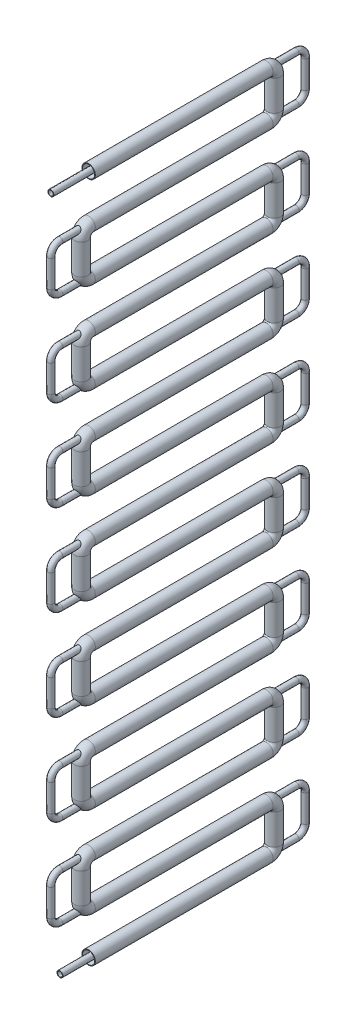
SolidWorks part; units mm, degrees
ref_plane "Alzado" through (0, 0, 0) normal (0, 0, 1) x (1, 0, 0)
ref_plane "Planta" through (0, 0, 0) normal (0, 1, 0) x (1, 0, 0)
ref_plane "Vista lateral" through (0, 0, 0) normal (1, 0, 0) x (0, 0, -1)
sketch "Seccion agua" plane through (0, 0, 0) normal (0, 0, 1) x (1, 0, 0)
  circle A2 centre (0, 0) radius 8
  circle A3 centre (0, 0) radius 8.8
  dimension "D1" = 16
  dimension "D2" = 0.8
sketch "Recorrido agua" plane through (0, 0, 0) normal (1, 0, 0) x (0, 0, -1)
  line L0 (0, 0) -> (235, 0)
  line L1 (245, -10) -> (245, -50)
  line L2 (235, -60) -> (0, -60)
  line L3 (-10, -70) -> (-10, -110)
  line L4 (0, -120) -> (235, -120)
  line L5 (0, 0) -> (0, -100.3636) construction
  line L6 (235, 0) -> (235, -103.1636) construction
  line L7 (245, -130) -> (245, -170)
  line L8 (235, -180) -> (0, -180)
  line L9 (-10, -190) -> (-10, -230)
  line L10 (0, -240) -> (235, -240)
  line L11 (245, -250) -> (245, -290)
  line L12 (235, -300) -> (0, -300)
  line L13 (-10, -310) -> (-10, -350)
  line L14 (0, -360) -> (235, -360)
  line L15 (245, -370) -> (245, -410)
  line L16 (235, -420) -> (0, -420)
  line L17 (-10, -430) -> (-10, -470)
  line L18 (0, -480) -> (235, -480)
  line L19 (245, -490) -> (245, -530)
  line L20 (235, -540) -> (0, -540)
  line L21 (-10, -550) -> (-10, -590)
  line L22 (0, -600) -> (235, -600)
  line L23 (245, -610) -> (245, -650)
  line L24 (235, -660) -> (0, -660)
  line L25 (-10, -670) -> (-10, -710)
  line L26 (0, -720) -> (235, -720)
  line L27 (245, -730) -> (245, -770)
  line L28 (235, -780) -> (0, -780)
  line L29 (-10, -790) -> (-10, -830)
  line L30 (0, -840) -> (235, -840)
  line L31 (245, -850) -> (245, -890)
  line L32 (235, -900) -> (0, -900)
  line L35 (0, -960) -> (235, -960) [skipped]
  line L36 (-10, -910) -> (-10, -950) [skipped]
  arc A0 (235, 0) -> (245, -10) centre (235, -10) cw
  arc A1 (245, -50) -> (235, -60) centre (235, -50) cw
  arc A2 (0, -60) -> (-10, -70) centre (0, -70) ccw
  arc A3 (-10, -110) -> (0, -120) centre (0, -110) ccw
  arc A4 (245, -170) -> (235, -180) centre (235, -170) cw
  arc A5 (0, -180) -> (-10, -190) centre (0, -190) ccw
  arc A6 (235, -120) -> (245, -130) centre (235, -130) cw
  arc A7 (-10, -230) -> (0, -240) centre (0, -230) ccw
  arc A8 (245, -290) -> (235, -300) centre (235, -290) cw
  arc A9 (0, -300) -> (-10, -310) centre (0, -310) ccw
  arc A10 (235, -240) -> (245, -250) centre (235, -250) cw
  arc A11 (-10, -350) -> (0, -360) centre (0, -350) ccw
  arc A12 (245, -410) -> (235, -420) centre (235, -410) cw
  arc A13 (0, -420) -> (-10, -430) centre (0, -430) ccw
  arc A14 (235, -360) -> (245, -370) centre (235, -370) cw
  arc A15 (-10, -470) -> (0, -480) centre (0, -470) ccw
  arc A16 (245, -530) -> (235, -540) centre (235, -530) cw
  arc A17 (0, -540) -> (-10, -550) centre (0, -550) ccw
  arc A18 (235, -480) -> (245, -490) centre (235, -490) cw
  arc A19 (-10, -590) -> (0, -600) centre (0, -590) ccw
  arc A20 (245, -650) -> (235, -660) centre (235, -650) cw
  arc A21 (0, -660) -> (-10, -670) centre (0, -670) ccw
  arc A22 (235, -600) -> (245, -610) centre (235, -610) cw
  arc A23 (-10, -710) -> (0, -720) centre (0, -710) ccw
  arc A24 (245, -770) -> (235, -780) centre (235, -770) cw
  arc A25 (0, -780) -> (-10, -790) centre (0, -790) ccw
  arc A26 (235, -720) -> (245, -730) centre (235, -730) cw
  arc A27 (-10, -830) -> (0, -840) centre (0, -830) ccw
  arc A28 (245, -890) -> (235, -900) centre (235, -890) cw
  arc A30 (235, -840) -> (245, -850) centre (235, -850) cw
  arc A32 (-10, -950) -> (0, -960) centre (0, -950) ccw [skipped]
  arc A33 (0, -900) -> (-10, -910) centre (0, -910) ccw [skipped]
  dimension "D1" = 10
  dimension "D2" = 60
  dimension "D3" = 235
  dimension "D4" = 8
sweep "Tuberia agua" add profiles "Seccion agua" path "Recorrido agua"
ref_plane "Plano refrigerante" through (0, 0, 50) normal (0, 0, 1) x (1, 0, 0)
sketch "Seccion refrigerante" plane through (0, 0, 50) normal (0, 0, 1) x (1, 0, 0)
  circle A0 centre (0, 0) radius 3.175
  circle A1 centre (0, 0) radius 3.975
  dimension "D1" = 0.8
  dimension "D2" = 6.35
sketch "Recorrido refrigerante" plane through (0, 0, 0) normal (1, 0, 0) x (0, 0, -1)
  line L0 (-50, 0) -> (274.2, 0)
  line L1 (-50, 3.975) -> (-50, -3.975) construction
  line L2 (286.2, -12) -> (286.2, -48)
  line L3 (274.2, -60) -> (-38, -60)
  line L4 (-50, 9.68) -> (-50, -9.68) construction
  line L5 (-50, -72) -> (-50, -108)
  line L6 (-38, -120) -> (274.2, -120)
  line L7 (274.2, -12) -> (274.2, -94.7312) construction
  line L8 (286.2, -132) -> (286.2, -168)
  line L10 (274.2, -180) -> (-38, -180)
  line L11 (-38, -240) -> (274.2, -240)
  line L12 (-50, -192) -> (-50, -228)
  line L13 (286.2, -252) -> (286.2, -288)
  line L14 (274.2, -300) -> (-38, -300)
  line L15 (-38, -360) -> (274.2, -360)
  line L16 (-50, -312) -> (-50, -348)
  line L17 (286.2, -372) -> (286.2, -408)
  line L18 (274.2, -420) -> (-38, -420)
  line L19 (-38, -480) -> (274.2, -480)
  line L20 (-50, -432) -> (-50, -468)
  line L21 (286.2, -492) -> (286.2, -528)
  line L22 (274.2, -540) -> (-38, -540)
  line L23 (-38, -600) -> (274.2, -600)
  line L24 (-50, -552) -> (-50, -588)
  line L25 (286.2, -612) -> (286.2, -648)
  line L26 (274.2, -660) -> (-38, -660)
  line L27 (-38, -720) -> (274.2, -720)
  line L28 (-50, -672) -> (-50, -708)
  line L29 (286.2, -732) -> (286.2, -768)
  line L30 (274.2, -780) -> (-38, -780)
  line L31 (-38, -840) -> (274.2, -840)
  line L32 (-50, -792) -> (-50, -828)
  line L33 (286.2, -852) -> (286.2, -888)
  line L34 (274.2, -900) -> (-38, -900)
  line L35 (236.2, -10) -> (236.2, -50) construction
  line L37 (-38, -960) -> (274.2, -960) [skipped]
  line L38 (-50, -912) -> (-50, -948) [skipped]
  arc A0 (274.2, 0) -> (286.2, -12) centre (274.2, -12) cw
  arc A1 (286.2, -48) -> (274.2, -60) centre (274.2, -48) cw
  arc A2 (-38, -60) -> (-50, -72) centre (-38, -72) ccw
  arc A3 (-50, -108) -> (-38, -120) centre (-38, -108) ccw
  arc A4 (274.2, -120) -> (286.2, -132) centre (274.2, -132) cw
  arc A5 (286.2, -168) -> (274.2, -180) centre (274.2, -168) cw
  arc A6 (-38, -180) -> (-50, -192) centre (-38, -192) ccw
  arc A7 (-50, -228) -> (-38, -240) centre (-38, -228) ccw
  arc A8 (274.2, -240) -> (286.2, -252) centre (274.2, -252) cw
  arc A9 (286.2, -288) -> (274.2, -300) centre (274.2, -288) cw
  arc A10 (-38, -300) -> (-50, -312) centre (-38, -312) ccw
  arc A11 (-50, -348) -> (-38, -360) centre (-38, -348) ccw
  arc A12 (274.2, -360) -> (286.2, -372) centre (274.2, -372) cw
  arc A13 (286.2, -408) -> (274.2, -420) centre (274.2, -408) cw
  arc A14 (-38, -420) -> (-50, -432) centre (-38, -432) ccw
  arc A15 (-50, -468) -> (-38, -480) centre (-38, -468) ccw
  arc A16 (274.2, -480) -> (286.2, -492) centre (274.2, -492) cw
  arc A17 (286.2, -528) -> (274.2, -540) centre (274.2, -528) cw
  arc A18 (-38, -540) -> (-50, -552) centre (-38, -552) ccw
  arc A19 (-50, -588) -> (-38, -600) centre (-38, -588) ccw
  arc A20 (274.2, -600) -> (286.2, -612) centre (274.2, -612) cw
  arc A21 (286.2, -648) -> (274.2, -660) centre (274.2, -648) cw
  arc A22 (-38, -660) -> (-50, -672) centre (-38, -672) ccw
  arc A23 (-50, -708) -> (-38, -720) centre (-38, -708) ccw
  arc A24 (274.2, -720) -> (286.2, -732) centre (274.2, -732) cw
  arc A25 (286.2, -768) -> (274.2, -780) centre (274.2, -768) cw
  arc A26 (-38, -780) -> (-50, -792) centre (-38, -792) ccw
  arc A27 (-50, -828) -> (-38, -840) centre (-38, -828) ccw
  arc A28 (274.2, -840) -> (286.2, -852) centre (274.2, -852) cw
  arc A29 (286.2, -888) -> (274.2, -900) centre (274.2, -888) cw
  arc A32 (-50, -948) -> (-38, -960) centre (-38, -948) ccw [skipped]
  arc A33 (-38, -900) -> (-50, -912) centre (-38, -912) ccw [skipped]
  dimension "D1" = 12
  dimension "D4" = 8
  dimension "D2" = 60
  dimension "D3" = 50
sweep "Tuberia refrigerante" add profiles "Seccion refrigerante" path "Recorrido refrigerante"
